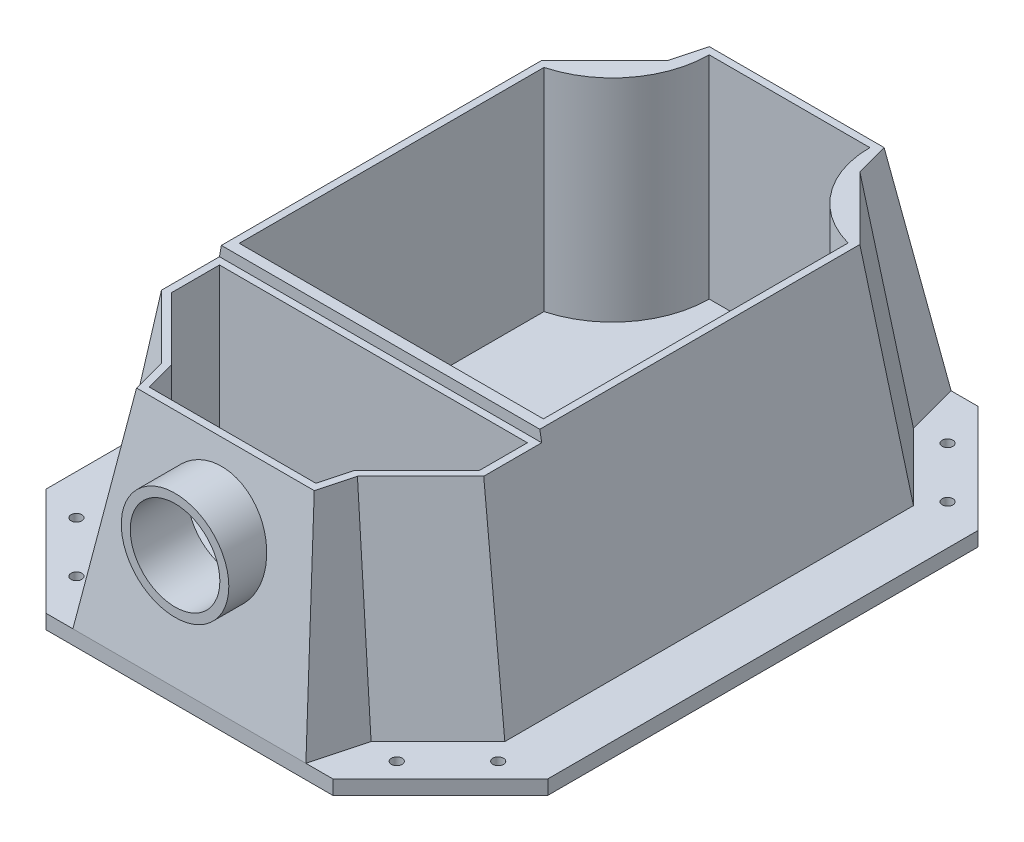
SolidWorks part; units mm, degrees
material "Polyetheretherketone (PEEK)"
ref_plane "Front Plane" through (0, 0, 0) normal (0, 0, 1) x (1, 0, 0)
ref_plane "Top Plane" through (0, 0, 0) normal (0, 1, 0) x (1, 0, 0)
ref_plane "Right Plane" through (0, 0, 0) normal (1, 0, 0) x (0, 0, -1)
sketch "Sketch1" plane through (0, 0, 0) normal (0, 1, 0) x (1, 0, 0)
  line L0 (-70, 60) -> (-40, 90)
  line L1 (-40, -90) -> (40, -90)
  line L2 (-70, -60) -> (-70, 60)
  line L3 (-40, 90) -> (40, 90)
  line L4 (70, -60) -> (70, 60)
  line L5 (-70, -90) -> (70, 90) construction
  line L6 (-70, 90) -> (70, -90) construction
  line L7 (0, 0) -> (0, 90) construction
  line L8 (0, 0) -> (70, 0) construction
  line L9 (40, 90) -> (70, 60)
  line L10 (-40, -90) -> (-70, -60)
  line L11 (40, -90) -> (70, -60)
  point P0 (0, 0)
  dimension "D1" = 140
  dimension "D2" = 180
extrude "Boss-Extrude1" add sketch "Sketch1" along normal blind 4
sketch "Sketch2" plane through (0, 4, 0) normal (0, 1, 0) x (1, 0, 0)
  line L0 (-70, 51.5147) -> (-33.5147, 88) construction
  line L4 (-51.7574, 69.7574) -> (-44.08, 62.08) construction
  line L5 (0, 0) -> (0, 21.4132) construction
  line L6 (0, 0) -> (12.8117, 0) construction
  line L7 (51.7574, 69.7574) -> (44.08, 62.08) construction
  line L8 (70, 51.5147) -> (33.5147, 88) construction
  line L9 (70, -51.5147) -> (33.5147, -88) construction
  line L10 (51.7574, -69.7574) -> (44.08, -62.08) construction
  line L11 (-51.7574, -69.7574) -> (-44.08, -62.08) construction
  line L12 (-70, -51.5147) -> (-33.5147, -88) construction
  line L13 (-70, 60) -> (-70, -60) construction
  line L14 (-70, 57.1716) -> (-39.1716, 88) construction
  line L15 (-39.1716, 88) -> (0, 88) construction
  line L16 (-40, 90) -> (-70, 60) construction
  line L17 (40, 90) -> (-40, 90) construction
  circle A0 centre (-58.8284, 62.6863) radius 1.5
  circle A1 centre (-44.6863, 76.8284) radius 1.5
  circle A4 centre (44.6863, 76.8284) radius 1.5
  circle A5 centre (58.8284, 62.6863) radius 1.5
  circle A6 centre (58.8284, -62.6863) radius 1.5
  circle A7 centre (44.6863, -76.8284) radius 1.5
  circle A8 centre (-44.6863, -76.8284) radius 1.5
  circle A9 centre (-58.8284, -62.6863) radius 1.5
  point P4 (-33.0103, 88.5044)
  point P5 (0, 0)
  point P47 (0, 0)
  point P48 (-33.0598, 88.4549)
  point P51 (0, 0)
  dimension "D1" = 10
  dimension "D2" = 3
  dimension "D3" = 4
  dimension "D4" = 2
  dimension "D5" = 2
extrude "Cut-Extrude1" cut sketch "Sketch2" against normal blind 90
sketch "Sketch4" plane through (0, 4, 0) normal (0, 1, 0) x (1, 0, 0)
  line L5 (-55, -57) -> (-55, 57)
  line L6 (-55, 57) -> (-36.3433, 75.6567)
  line L7 (-36.3433, 75.6567) -> (-32.5, 90)
  line L20 (40, 90) -> (-40, 90) construction
  line L21 (-32.5, 90) -> (32.5, 90)
  line L22 (0, 90) -> (0, 0) construction
  line L23 (0, 0) -> (70, 0) construction
  line L24 (70, -60) -> (70, 60) construction
  line L25 (36.3433, 75.6567) -> (32.5, 90)
  line L26 (55, 57) -> (36.3433, 75.6567)
  line L27 (55, -57) -> (55, 57)
  line L28 (-40, 90) -> (-70, 60) construction
  line L29 (-55, -57) -> (-36.3433, -75.6567)
  line L30 (-36.3433, -75.6567) -> (-32.5, -90)
  line L31 (-32.5, -90) -> (32.5, -90)
  line L32 (36.3433, -75.6567) -> (32.5, -90)
  line L33 (55, -57) -> (36.3433, -75.6567)
  point P2 (-56.8147, 0)
  point P15 (0, 0)
  point P22 (-36.5514, 75.4486)
  point P24 (-55, 0)
  point P30 (55, 0)
  dimension "D1" = 65
  dimension "D2" = 110
  dimension "D3" = 57
  dimension "D4" = 75
extrude "Boss-Extrude2" add sketch "Sketch4" along normal blind 60 draft 10 contours L25 L21 L7 L6 L5 L29 L30 L31 L32 L33 L27 L26
sketch "Sketch7" plane through (0, 64, 0) normal (0, 1, 0) x (1, 0, 0)
  line L0 (0, 0) -> (0, 79.4204) construction
  line L1 (-24.382, 79.4204) -> (24.382, 79.4204) construction
  line L2 (22.4085, 77.4204) -> (-22.4085, 77.4204)
  line L3 (-42.4204, 51.3404) -> (-42.4204, -33.6596)
  line L4 (-44.4204, -52.6178) -> (-44.4204, 52.6178) construction
  line L5 (42.4204, 51.3404) -> (42.4204, -33.6596)
  line L6 (42.4204, -33.6596) -> (-42.4204, -33.6596)
  line L22 (87.6206, -100.369) -> (-87.6206, -100.369)
  line L23 (87.6206, -100.369) -> (87.6206, -36.6596)
  line L24 (87.6206, -36.6596) -> (-87.6206, -36.6596)
  line L25 (-87.6206, -100.369) -> (-87.6206, -36.6596)
  line L26 (87.6206, -100.369) -> (-87.6206, -36.6596) construction
  line L27 (87.6206, -36.6596) -> (-87.6206, -100.369) construction
  arc A0 (-22.4085, 77.4204) -> (-42.4204, 51.3404) centre (-49.4085, 77.4204) cw
  arc A1 (22.4085, 77.4204) -> (42.4204, 51.3404) centre (49.4085, 77.4204) ccw
  point P9 (0, -68.5143)
  point P17 (0, 77.4204)
  point P20 (0, -69.9403)
  dimension "D1" = 2
  dimension "D3" = 27
  dimension "D2" = 2
  dimension "D4" = 75
  dimension "D5" = 85
  dimension "D6" = 3
extrude "Cut-Extrude4" cut sketch "Sketch7" against normal blind 3
sketch "Sketch11" plane through (0, 61, 0) normal (0, 1, 0) x (1, 0, 0)
  line L4 (-42.4204, 51.3404) -> (-42.4204, -33.6596)
  line L5 (-42.4204, -33.6596) -> (42.4204, -33.6596)
  line L6 (42.4204, -33.6596) -> (42.4204, 51.3404)
  line L7 (22.4085, 77.4204) -> (-22.4085, 77.4204)
  line L8 (-42.4204, 51.3404) -> (-42.4204, -33.6596)
  line L9 (-42.4204, -33.6596) -> (42.4204, -33.6596)
  line L10 (42.4204, -33.6596) -> (42.4204, 51.3404)
  line L11 (22.4085, 77.4204) -> (-22.4085, 77.4204)
  arc A2 (-42.4204, 51.3404) -> (-22.4085, 77.4204) centre (-49.4085, 77.4204) ccw
  arc A3 (22.4085, 77.4204) -> (42.4204, 51.3404) centre (49.4085, 77.4204) ccw
  arc A4 (-42.4204, 51.3404) -> (-22.4085, 77.4204) centre (-49.4085, 77.4204) ccw
  arc A5 (22.4085, 77.4204) -> (42.4204, 51.3404) centre (49.4085, 77.4204) ccw
  dimension "D1" = 0
extrude "Cut-Extrude5" cut sketch "Sketch11" against normal blind 56
sketch "Sketch12" plane through (0, 61, 0) normal (0, 1, 0) x (1, 0, 0)
  line L16 (-42.9494, -52.0085) -> (-25.539, -69.4189)
  line L17 (-25.539, -69.4189) -> (-23.2532, -77.9494)
  line L18 (-23.2532, -77.9494) -> (23.2532, -77.9494)
  line L19 (23.2532, -77.9494) -> (25.539, -69.4189)
  line L20 (25.539, -69.4189) -> (42.9494, -52.0085)
  line L21 (42.9494, -52.0085) -> (42.9494, -38.6596)
  line L22 (42.9494, -38.6596) -> (-42.9494, -38.6596)
  line L23 (-42.9494, -38.6596) -> (-42.9494, -52.0085)
  line L24 (-42.9494, -52.0085) -> (-25.539, -69.4189)
  line L25 (-25.539, -69.4189) -> (-23.2532, -77.9494)
  line L26 (-23.2532, -77.9494) -> (23.2532, -77.9494)
  line L27 (23.2532, -77.9494) -> (25.539, -69.4189)
  line L28 (25.539, -69.4189) -> (42.9494, -52.0085)
  line L29 (42.9494, -52.0085) -> (42.9494, -38.6596)
  line L30 (42.9494, -38.6596) -> (-42.9494, -38.6596)
  line L31 (-42.9494, -38.6596) -> (-42.9494, -52.0085)
  dimension "D1" = 2
extrude "Cut-Extrude6" cut sketch "Sketch12" against normal blind 56
ref_plane "Plane1" through (0, 0, 94) normal (0, 0, 1) x (1, 0, 0)
sketch "Sketch5" plane through (0, 0, 94) normal (0, 0, 1) x (1, 0, 0)
  line L0 (0, 0) -> (0, 40) construction
  circle A0 centre (0, 40) radius 15
  point P4 (0, 39.8294)
  dimension "D1" = 30
  dimension "D2" = 40
extrude "Boss-Extrude3" add sketch "Sketch5" against normal up to surface (10.3478 mm away) up to face at (0, 32.5, 84.9747)
sketch "Sketch6" plane through (0, 0, 94) normal (0, 0, 1) x (1, 0, 0)
  circle A0 centre (0, 40) radius 12.5
  dimension "D1" = 25
extrude "Cut-Extrude3" cut sketch "Sketch6" against normal blind 40
sketch "Sketch14" plane through (0, 5, 0) normal (0, 1, 0) x (1, 0, 0)
  ellipse E0 centre (0, -49.6528) end of major axis (22.7346, -49.6528) minor radius 6.1653
extrude "Cut-Extrude8" cut sketch "Sketch14" against normal blind 56
